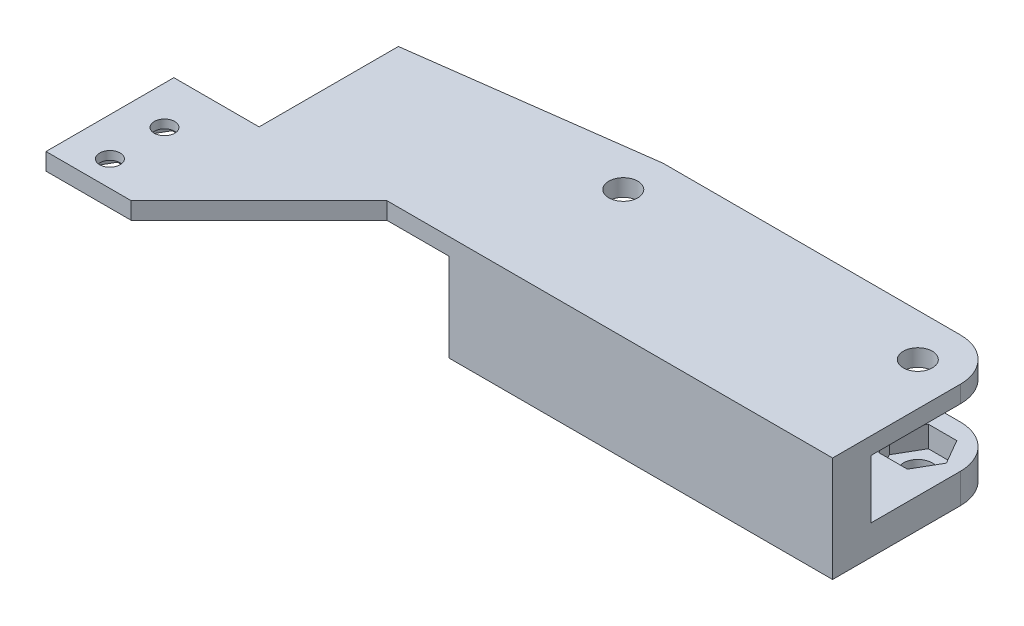
SolidWorks part; units mm, degrees
ref_plane "Front Plane" through (0, 0, 0) normal (0, 0, 1) x (1, 0, 0)
ref_plane "Top Plane" through (0, 0, 0) normal (0, 1, 0) x (1, 0, 0)
ref_plane "Right Plane" through (0, 0, 0) normal (1, 0, 0) x (0, 0, -1)
sketch "Sketch1" plane through (0, 0, 0) normal (0, 1, 0) x (1, 0, 0)
  line L0 (0, 0) -> (34.55, 0) construction
  line L1 (-37.725, 0) -> (72.275, 0) construction
  line L2 (-0.6627, 4.9559) -> (-29.0504, 1.16)
  line L3 (-37.725, -8.7518) -> (-37.725, -30)
  line L4 (-37.725, -30) -> (-27.725, -30)
  line L5 (-27.725, -30) -> (-27.725, -15)
  line L6 (0, 5) -> (34.55, 5)
  line L7 (-27.725, -15) -> (39.55, -15)
  line L8 (39.55, -15) -> (39.55, 0)
  line L9 (-27.725, -15) -> (-37.725, -15)
  line L10 (-27.725, -15) -> (-27.725, 1.3372)
  line L11 (-27.725, -30) -> (-12.725, -15)
  circle A0 centre (0, 0) radius 1.7
  circle A1 centre (34.55, 0) radius 1.7
  circle A2 centre (0, 0) radius 5
  circle A3 centre (34.55, 0) radius 5
  arc A5 (-37.725, -8.7518) -> (-29.0504, 1.16) centre (-27.725, -8.7518) cw
  point P9 (17.275, 0)
  point P10 (17.275, 0)
  point P22 (-24.397, 1.7822)
  dimension "D1" = 3.4
  dimension "D2" = 34.55
  dimension "D3" = 10
  dimension "D4" = 10
  dimension "D6" = 30
  dimension "D9" = 10
  dimension "D5" = 110
  dimension "D7" = 15
  dimension "D8" = 10
  dimension "D10" = 15
extrude "Boss-Extrude1" add sketch "Sketch1" along normal blind 2 contours A2 A0 | A3 L6 A2 | A3 A1 | L5 L9 L3 L4 | L5 L11 L7 region at (5.2683, 0, 6.1241) region at (-0.3227, 0, -4.8479) region at (-22.725, 0, 20) region at (-32.725, 0, 22.5) region at (37.9855, 0, -3.4355)
sketch "Sketch2" plane through (0, 0, 0) normal (0, -1, 0) x (1, 0, 0)
  line L1 (39.55, 15) -> (-5.45, 15)
  line L2 (39.55, 15) -> (39.55, 10.5)
  line L3 (39.55, 10.5) -> (-5.45, 10.5)
  line L4 (-5.45, 15) -> (-5.45, 10.5)
  point P4 (39.55, 15)
  dimension "D1" = 4.5
  dimension "D2" = 45
extrude "Boss-Extrude2" add sketch "Sketch2" along normal blind 6.85
sketch "Sketch3" plane through (0, -6.85, 0) normal (0, -1, 0) x (1, 0, 0)
  line L0 (-5.45, 10.5) -> (-5.45, -4.3157)
  line L1 (36.2243, 2.9) -> (32.8757, 2.9)
  line L2 (32.8757, 2.9) -> (31.2014, 0)
  line L3 (31.2014, 0) -> (32.8757, -2.9)
  line L4 (32.8757, -2.9) -> (36.2243, -2.9)
  line L5 (36.2243, -2.9) -> (37.8986, 0)
  line L6 (37.8986, 0) -> (36.2243, 2.9)
  line L7 (1.6743, 2.9) -> (-1.6743, 2.9)
  line L8 (-1.6743, 2.9) -> (-3.3486, 0)
  line L9 (-3.3486, 0) -> (-1.6743, -2.9)
  line L10 (-1.6743, -2.9) -> (1.6743, -2.9)
  line L11 (1.6743, -2.9) -> (3.3486, 0)
  line L12 (3.3486, 0) -> (1.6743, 2.9)
  line L13 (-5.45, 15) -> (39.55, 15)
  line L14 (39.55, 15) -> (39.55, 10.5)
  line L15 (-0.6627, -4.9559) -> (-27.725, -1.3372) construction
  line L31 (-5.45, 10.5) -> (-5.45, 15)
  line L36 (-5.45, -4.3157) -> (-0.6627, -4.9559)
  line L37 (0, -5) -> (34.55, -5)
  line L38 (39.55, 0) -> (39.55, 10.5)
  circle A0 centre (34.55, 0) radius 2.9 construction
  circle A1 centre (0, 0) radius 2.9 construction
  arc A2 (34.55, -5) -> (39.55, 0) centre (34.55, 0) ccw construction
  arc A9 (-0.6627, -4.9559) -> (0, -5) centre (0, 0) ccw
  arc A10 (34.55, -5) -> (39.55, 0) centre (34.55, 0) ccw
  point P0 (0, 0)
  point P1 (34.7222, 0)
  point P30 (3.7852, 4.4317)
  point P31 (-0.2377, 0)
  line M25 (39.55, 10.5) -> (39.55, 15)
  line M26 (39.55, 15) -> (-5.45, 15)
  line M27 (-5.45, 15) -> (-5.45, 10.5)
  line M28 (-5.45, 10.5) -> (39.55, 10.5)
  dimension "D1" = 5.8
extrude "Boss-Extrude3" add sketch "Sketch3" along normal blind 3.5 contours L5 L6 L1 L2 L3 L4 | L11 L12 L7 L8 L9 L10 | L37 A10 L38 L0 L36 A9 L6 L5 L4 L3 L2 L1 L12 L11 L10 L9 L8 L7 M28 | M28 M25 M26 M27 region at (16.9054, -6.85, 3.0806) region at (17.05, -6.85, 12.75) region at (34.55, -6.85, 0) region at (0, -6.85, 0)
extrude "Cut-Extrude1" cut sketch "Sketch3<3>" along normal blind 2.5 contours L5 L6 L1 L2 L3 L4 | L11 L12 L7 L8 L9 L10 region at (34.55, -6.85, 0) region at (0, -6.85, 0)
sketch "Sketch3<3>" plane through (0, -6.85, 0) normal (0, -1, 0) x (1, 0, 0) same geometry as "Sketch3"
sketch "Sketch4" plane through (0, 2, 0) normal (0, 1, 0) x (1, 0, 0)
  line L2 (-37.725, -15) -> (-37.725, -30) construction
  line L3 (-37.725, -30) -> (-27.725, -30) construction
  circle A0 centre (-33.225, -20.6) radius 1.2
  circle A1 centre (-33.225, -27) radius 1.2
  point P8 (0, 0)
  dimension "D1" = 2.4
  dimension "D2" = 6.4
  dimension "D3" = 4.5
  dimension "D4" = 3
extrude "Cut-Extrude2" cut sketch "Sketch4" against normal up to next
sketch "Sketch5" plane through (0, 0, 0) normal (0, -1, 0) x (1, 0, 0)
  line L1 (-32.0126, 22.7) -> (-34.4374, 22.7)
  line L2 (-34.4374, 22.7) -> (-35.6499, 20.6)
  line L3 (-35.6499, 20.6) -> (-34.4374, 18.5)
  line L4 (-34.4374, 18.5) -> (-32.0126, 18.5)
  line L5 (-32.0126, 18.5) -> (-30.8001, 20.6)
  line L6 (-30.8001, 20.6) -> (-32.0126, 22.7)
  line L7 (-32.0126, 29.1) -> (-34.4374, 29.1)
  line L8 (-34.4374, 29.1) -> (-35.6499, 27)
  line L9 (-35.6499, 27) -> (-34.4374, 24.9)
  line L10 (-34.4374, 24.9) -> (-32.0126, 24.9)
  line L11 (-32.0126, 24.9) -> (-30.8001, 27)
  line L12 (-30.8001, 27) -> (-32.0126, 29.1)
  circle A0 centre (-33.225, 20.6) radius 2.1 construction
  circle A1 centre (-33.225, 27) radius 2.1 construction
  dimension "D1" = 4.2
extrude "Cut-Extrude3" cut sketch "Sketch5" against normal blind 1
sketch "Sketch6" plane through (0, -10.35, 0) normal (0, -1, 0) x (1, 0, 0)
  circle A0 centre (0, 0) radius 1.7
  circle A1 centre (34.55, 0) radius 1.7
  dimension "D1" = 3.4
extrude "Cut-Extrude4" cut sketch "Sketch6" against normal up to next
